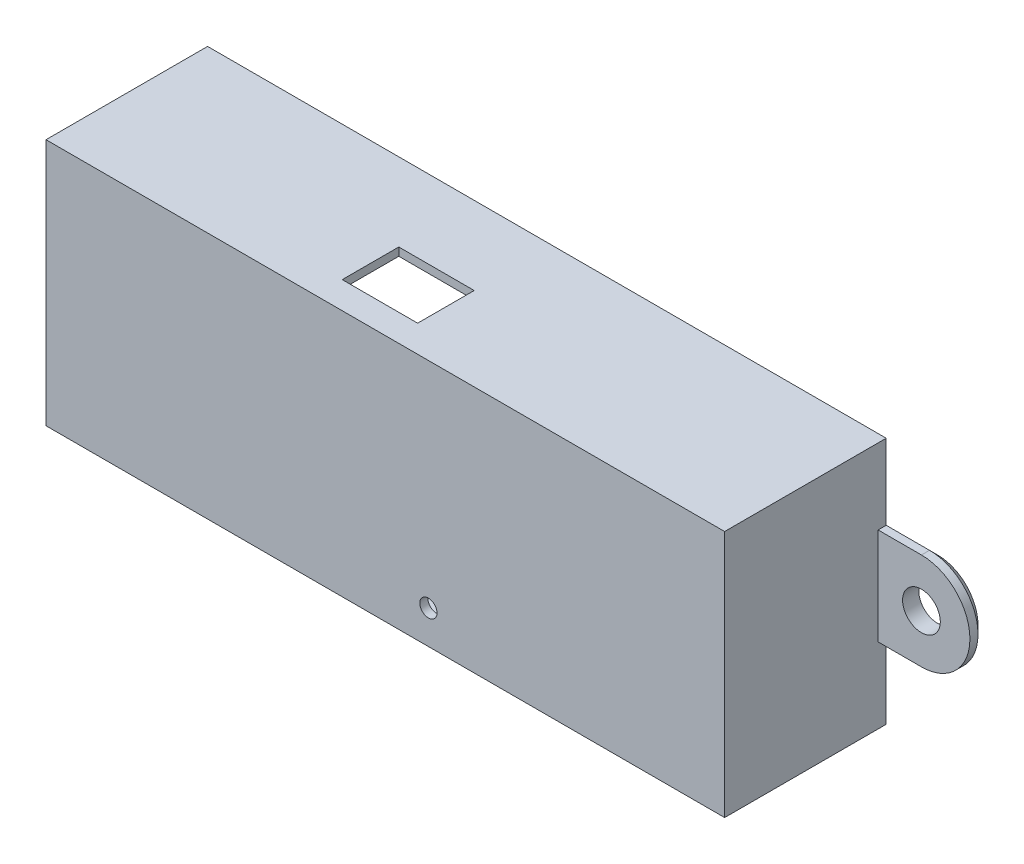
SolidWorks part; units mm, degrees
ref_plane "Спереди" through (0, 0, 0) normal (0, 0, 1) x (1, 0, 0)
ref_plane "Сверху" through (0, 0, 0) normal (0, 1, 0) x (1, 0, 0)
ref_plane "Справа" through (0, 0, 0) normal (1, 0, 0) x (0, 0, -1)
sketch "Эскиз1" plane through (0, 0, 0) normal (0, 0, 1) x (1, 0, 0)
  line L5 (0, 0) -> (123, 0)
  line L6 (0, 0) -> (0, 43)
  line L7 (0, 43) -> (123, 43)
  line L8 (123, 0) -> (123, 43)
  dimension "D1" = 123
  dimension "D2" = 43
extrude "Бобышка-Вытянуть1" add sketch "Эскиз1" along normal blind 1.5
sketch "Эскиз2" plane through (0, 0, 0) normal (0, 0, -1) x (-1, 0, 0)
  line L1 (-124.5, -1.5) -> (1.5, -1.5)
  line L2 (-124.5, -1.5) -> (-124.5, 44.5)
  line L3 (-124.5, 44.5) -> (1.5, 44.5)
  line L4 (1.5, -1.5) -> (1.5, 44.5)
  line L9 (-123, 0) -> (0, 0)
  line L10 (-123, 0) -> (-123, 43)
  line L11 (-123, 43) -> (0, 43)
  line L12 (0, 0) -> (0, 43)
  dimension "D1" = 1.5
  dimension "D2" = 1.5
  dimension "D3" = 1.5
  dimension "D4" = 1.5
extrude "Бобышка-Вытянуть2" add sketch "Эскиз2" along normal blind 30 and the other way blind 1.5
sketch "Эскиз3" plane through (0, 0, -30) normal (0, 0, -1) x (-1, 0, 0)
  line L0 (-124.5, 12.5) -> (-132.54, 12.5)
  line L1 (-124.5, 30.5) -> (-132.54, 30.5)
  line L2 (-134.7332, 21.5) -> (-136.04, 21.5) construction
  line L3 (-124.5, 30.5) -> (-124.5, 12.5)
  line L4 (-123, 21.5) -> (0, 21.5) construction
  line L5 (-123, 43) -> (-123, 0) construction
  line L6 (0, 0) -> (0, 43) construction
  line L7 (-124.5, 44.5) -> (-124.5, -1.5) construction
  arc A0 (-132.54, 12.5) -> (-132.54, 30.5) centre (-132.54, 21.5) cw
  circle A1 centre (-132.54, 21.5) radius 3.5
  dimension "D1" = 7
  dimension "D3" = 9
  dimension "D2" = 9
  dimension "D4" = 8.04
extrude "Бобышка-Вытянуть3" add sketch "Эскиз3" against normal blind 3
ref_plane "Плоскость1" through (61.5, 0, 0) normal (1, 0, 0) x (0, 0, -1)
mirror "Зеркальное отражение1" about plane through (61.5, 0, 0) normal (1, 0, 0) of "Бобышка-Вытянуть3"
ref_plane "Плоскость2" through (123, 43, -30) normal (0, 0, -1) x (-1, 0, 0)
sketch "Эскиз5" plane through (0, 0, 1.5) normal (0, 0, 1) x (1, 0, 0)
  circle A0 centre (69.5, 4.7) radius 1.6
  dimension "D5" = 3.2
  dimension "D6" = 55
  dimension "D7" = 6.2
extrude "Вырез-Вытянуть1" cut sketch "Эскиз5" against normal blind 10
sketch "Эскиз6" plane through (-1.5, 0, 0) normal (-1, 0, 0) x (0, 0, 1)
  line L0 (-20, 17.3) -> (-22.5, 17.3)
  line L6 (-24.5, 9.65) -> (-24.5, 16.65)
  line L8 (-20, 9) -> (-20, 17.3)
  line L9 (-22.5, 17.3) -> (-22.5, 16.65)
  line L10 (-22.5, 16.65) -> (-24.5, 16.65)
  line L11 (-20, 9) -> (-22.5, 9)
  line L12 (-22.5, 9) -> (-22.5, 9.65)
  line L13 (-22.5, 9.65) -> (-24.5, 9.65)
  line L17 (1.5, -1.5) -> (-30, -1.5) construction
  line L18 (-30, -1.5) -> (-30, 12.5) construction
  dimension "D1" = 7
  dimension "D2" = 8.3
  dimension "D3" = 4.5
  dimension "D4" = 2.5
  dimension "D5" = 10.5
  dimension "D6" = 5.5
extrude "Вырез-Вытянуть2" cut sketch "Эскиз6" against normal blind 10
chamfer "Фаска1" distance 1.5 angle 45 12 edges at (-1.5, 37.5, -30) (-5.52, 30.5, -30) (-18.54, 21.5, -30) (-5.52, 12.5, -30) (-1.5, 5.5, -30) (61.5, -1.5, -30) (124.5, 5.5, -30) (128.52, 12.5, -30) (141.54, 21.5, -30) (128.52, 30.5, -30) (61.5, 44.5, -30) (124.5, 37.5, -30)
sketch "Эскиз7" plane through (0, 44.5, 0) normal (0, 1, 0) x (1, 0, 0)
  line L0 (-1.5, -1.5) -> (-1.5, 28.5) construction
  line L1 (48.5, 3.5) -> (62.5, 3.5)
  line L2 (48.5, 3.5) -> (48.5, 14)
  line L3 (48.5, 14) -> (62.5, 14)
  line L4 (62.5, 3.5) -> (62.5, 14)
  line L5 (-1.5, -1.5) -> (124.5, -1.5) construction
  dimension "D1" = 14
  dimension "D2" = 10.5
  dimension "D3" = 50
  dimension "D4" = 5
extrude "Вырез-Вытянуть3" cut sketch "Эскиз7" against normal blind 10
